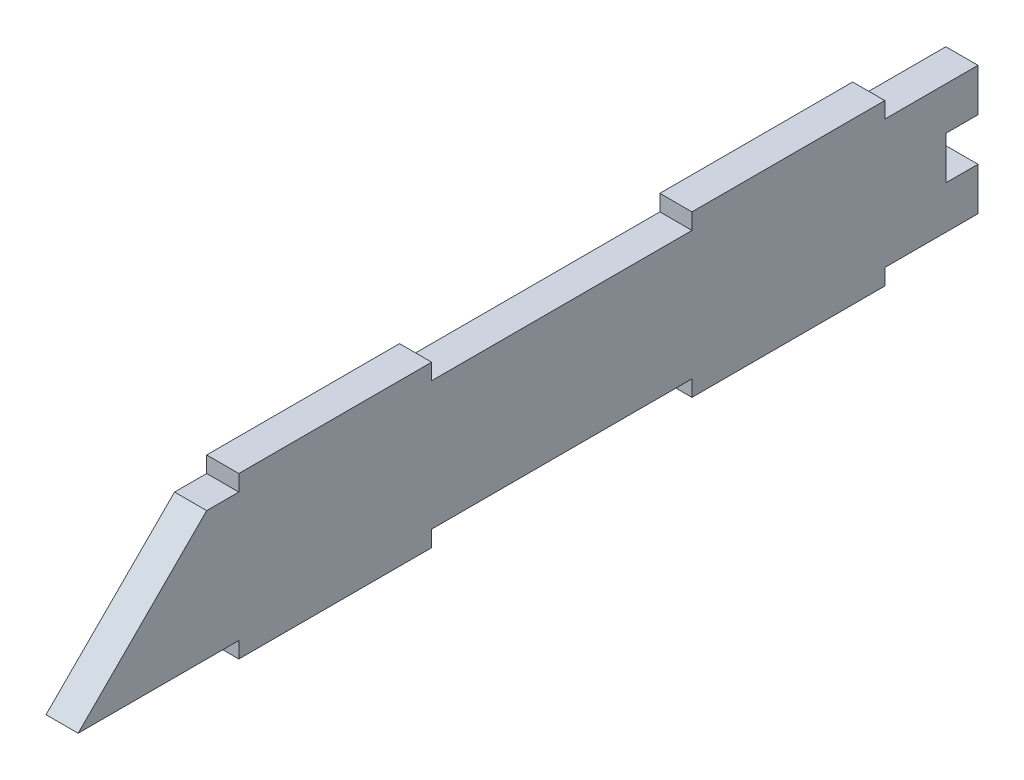
SolidWorks part; units mm, degrees
ref_plane "Front Plane" through (0, 0, 0) normal (0, 0, 1) x (1, 0, 0)
ref_plane "Top Plane" through (0, 0, 0) normal (0, 1, 0) x (1, 0, 0)
ref_plane "Right Plane" through (0, 0, 0) normal (1, 0, 0) x (0, 0, -1)
sketch "Sketch1" plane through (0, 0, 0) normal (1, 0, 0) x (0, 0, -1)
  line L1 (-177.8, -25.4) -> (177.8, -25.4)
  line L2 (-177.8, -25.4) -> (-177.8, 25.4)
  line L3 (-177.8, 25.4) -> (177.8, 25.4)
  line L4 (177.8, -25.4) -> (177.8, 25.4)
  line L5 (-177.8, -25.4) -> (177.8, 25.4) construction
  line L6 (-177.8, 25.4) -> (177.8, -25.4) construction
  point P0 (0, 0)
  dimension "D1" = 355.6
  dimension "D2" = 50.8
extrude "Boss-Extrude1" add sketch "Sketch1" along normal blind 12.7
sketch "Sketch2" plane through (12.7, 0, 0) normal (1, 0, 0) x (0, 0, -1)
  line L0 (-177.8, -25.4) -> (-127, 25.4)
  line L1 (177.8, 25.4) -> (-177.8, 25.4) construction
  dimension "D1" = 50.8
extrude "Cut-Extrude1" cut sketch "Sketch2" against normal through all and the other way through all
sketch "Sketch3" plane through (0, 0, 0) normal (-1, 0, 0) x (0, 0, 1)
  line L0 (177.8, -25.4) -> (-177.8, -25.4) construction
  line L1 (-140.97, -25.4) -> (-64.77, -25.4)
  line L2 (-140.97, -25.4) -> (-140.97, -31.75)
  line L3 (-140.97, -31.75) -> (-64.77, -31.75)
  line L4 (-64.77, -25.4) -> (-64.77, -31.75)
  line L5 (-177.8, -25.4) -> (-177.8, 25.4) construction
  line L6 (38.1, -25.4) -> (114.3, -25.4)
  line L7 (38.1, -25.4) -> (38.1, -31.75)
  line L8 (38.1, -31.75) -> (114.3, -31.75)
  line L9 (114.3, -25.4) -> (114.3, -31.75)
  line L10 (-177.8, 25.4) -> (127, 25.4) construction
  line L11 (-140.97, 25.4) -> (-64.77, 25.4)
  line L12 (-140.97, 25.4) -> (-140.97, 31.75)
  line L13 (-140.97, 31.75) -> (-64.77, 31.75)
  line L14 (-64.77, 25.4) -> (-64.77, 31.75)
  line L16 (38.1, 25.4) -> (114.3, 25.4)
  line L17 (38.1, 25.4) -> (38.1, 31.75)
  line L18 (38.1, 31.75) -> (114.3, 31.75)
  line L19 (114.3, 25.4) -> (114.3, 31.75)
  dimension "D1" = 76.2
  dimension "D2" = 6.35
  dimension "D3" = 76.2
  dimension "D4" = 6.35
  dimension "D5" = 36.83
  dimension "D6" = 215.9
  dimension "D7" = 76.2
  dimension "D8" = 6.35
  dimension "D9" = 6.35
  dimension "D10" = 76.2
extrude "Boss-Extrude2" add sketch "Sketch3" against normal blind 12.7
sketch "Sketch4" plane through (0, 0, 0) normal (-1, 0, 0) x (0, 0, 1)
  line L0 (-177.8, -25.4) -> (-177.8, 25.4) construction
  line L1 (-177.8, 8.4667) -> (-165.1, 8.4667)
  line L2 (-177.8, 8.4667) -> (-177.8, -8.4667)
  line L3 (-177.8, -8.4667) -> (-165.1, -8.4667)
  line L4 (-165.1, 8.4667) -> (-165.1, -8.4667)
  line L5 (-140.97, -25.4) -> (-177.8, -25.4) construction
  dimension "D1" = 16.9333
  dimension "D2" = 16.9333
  dimension "D3" = 12.7
extrude "Cut-Extrude2" cut sketch "Sketch4" against normal through all
